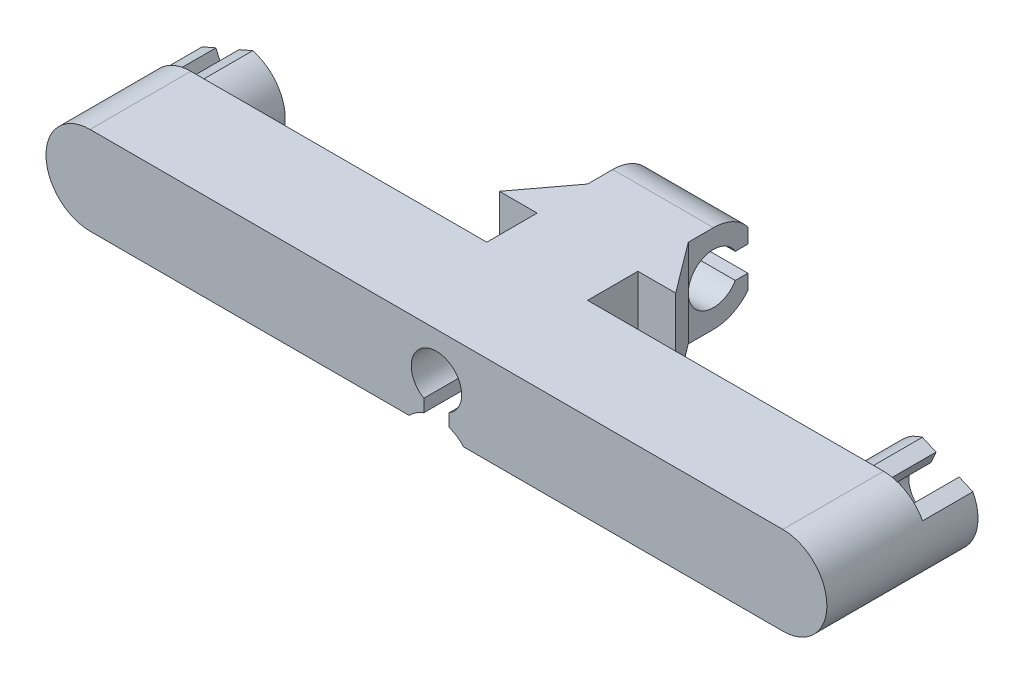
SolidWorks part; units mm, degrees
ref_plane "前视基准面" through (0, 0, 0) normal (0, 0, 1) x (1, 0, 0)
ref_plane "上视基准面" through (0, 0, 0) normal (0, 1, 0) x (1, 0, 0)
ref_plane "右视基准面" through (0, 0, 0) normal (1, 0, 0) x (0, 0, -1)
other "Configuration Table"
sketch "草图1" plane through (0, 0, 0) normal (0, 0, 1) x (1, 0, 0)
  line L0 (-404.5156, 0) -> (19821.2627, 0) construction
  line L1 (0, -404.5156) -> (0, 19821.2627) construction
  line L2 (-13.7534, 1.75) -> (13.7534, 1.75)
  line L3 (-13.7534, -1.75) -> (13.7534, -1.75)
  arc A0 (-13.7534, 1.75) -> (-13.7534, -1.75) centre (-13.7534, 0) ccw
  arc A1 (13.7534, 1.75) -> (13.7534, -1.75) centre (13.7534, 0) cw
  dimension "D1" = 3.5
  dimension "D2" = 27.5068
extrude "凸台-拉伸1" add sketch "草图1" along normal blind 4
sketch "草图2" plane through (0, 0, 0) normal (0, 0, -1) x (-1, 0, 0)
  line L0 (13.7534, -1.75) -> (-13.7534, -1.75) construction
  line L1 (-2, 1.75) -> (2, 1.75)
  line L2 (-2, 1.75) -> (-2, -1.75)
  line L3 (-2, -1.75) -> (2, -1.75)
  line L4 (2, 1.75) -> (2, -1.75)
  line L5 (-2, 1.75) -> (2, -1.75) construction
  line L6 (-2, -1.75) -> (2, 1.75) construction
  point P0 (0, 0)
  dimension "D1" = 4
extrude "凸台-拉伸2" add sketch "草图2" along normal blind 2
sketch "草图3" plane through (0, 1.75, 0) normal (0, 1, 0) x (1, 0, 0)
  line L0 (0, -1000) -> (0, 49000) construction
  line L1 (3.5, 2) -> (-3.5, 2)
  line L2 (-2, 2) -> (2, 2) construction
  line L3 (-3.5, 2) -> (-2, 4)
  line L4 (-2, 4) -> (2, 4)
  line L5 (3.5, 2) -> (2, 4)
  point P1 (0, 4)
  point P11 (0, 2)
  dimension "D1" = 3.5
  dimension "D2" = 2
  dimension "D3" = 2
extrude "凸台-拉伸3" add sketch "草图3" against normal blind 3.5
sketch "草图4" plane through (0, 0, 0) normal (0, 0, -1) x (-1, 0, 0)
  line L0 (0, -1000) -> (0, 49000) construction
  circle A0 centre (-13.7534, 0) radius 1.75
  circle A1 centre (13.7534, 0) radius 1.75
  dimension "D1" = 3.5
extrude "凸台-拉伸4" add sketch "草图4" along normal blind 2
sketch "草图5" plane through (0, 0, 4) normal (0, 0, 1) x (1, 0, 0)
  line L0 (0, -1000) -> (0, 49000) construction
  line L1 (-0.5, -1.75) -> (-0.5, -0.866)
  line L2 (-13.7534, -1.75) -> (13.7534, -1.75) construction
  line L3 (0.5, -1.75) -> (0.5, -0.866)
  line L4 (-0.5, -1.75) -> (0.5, -1.75)
  line L5 (-0.5, -1.366) -> (0.5, -1.366)
  line L6 (-0.5, -1.75) -> (-1.0795, -1.75)
  line L7 (0.5, -1.75) -> (1.0795, -1.75)
  arc A0 (0.5, -0.866) -> (-0.5, -0.866) centre (0, 0) ccw
  circle A1 centre (0, -2.75) radius 1.4715
  dimension "D1" = 2
  dimension "D2" = 0.5
  dimension "D3" = 0.5
  dimension "D4" = 1
extrude "切除-拉伸2" cut sketch "草图5" against normal blind 2 contours L1 A1 L7 | L5 L0 A1 | L0 L5 A1 | L7 L0 L5 L1 | L0 L4 L3 L5 | L7 A1 L3 | L0 A1 L3 A0 | A1 L0 A0 L1 region at (-0.25, -1.558, 4) region at (0.25, -1.558, 4) region at (-0.7089, -1.6105, 4) region at (-0.1883, -1.3309, 4) region at (0.1883, -1.3309, 4) region at (0.7089, -1.6105, 4) region at (-0.4095, -0.1135, 4) region at (0.4095, -0.1135, 4)
ref_plane "基准面1" through (0, 0, 0) normal (0, 1, 0) x (1, 0, 0)
sketch "草图6" plane through (0, 0, -2) normal (0, 0, -1) x (-1, 0, 0)
  line L0 (-1000, 0) -> (49000, 0) construction
  line L1 (0, -1000) -> (0, 49000) construction
  line L2 (13.7534, 0) -> (16.6021, 6.5623) construction
  line L3 (13.6396, 0.9935) -> (13.8387, 1.4522)
  line L4 (14.5569, 0.5953) -> (14.756, 1.054)
  line L5 (-14.5569, 0.5953) -> (-14.756, 1.054)
  line L6 (-13.6396, 0.9935) -> (-13.8387, 1.4522)
  line L7 (-14.756, 1.054) -> (-15.3007, 0.8175)
  line L8 (13.8387, 1.4522) -> (13.294, 1.6886)
  line L9 (14.756, 1.054) -> (15.3007, 0.8175)
  line L10 (-13.8387, 1.4522) -> (-13.294, 1.6886)
  circle A0 centre (13.7534, 0) radius 1.75 construction
  arc A2 (13.6396, 0.9935) -> (14.5569, 0.5953) centre (13.7534, 0) ccw
  arc A3 (14.8799, 1.3393) -> (13.9626, 1.7375) centre (13.7534, 0) ccw
  arc A4 (-13.6396, 0.9935) -> (-14.5569, 0.5953) centre (-13.7534, 0) cw
  arc A5 (-14.8799, 1.3393) -> (-13.9626, 1.7375) centre (-13.7534, 0) cw
  arc A6 (15.3007, 0.8175) -> (13.294, 1.6886) centre (13.7534, 0) ccw
  arc A7 (-15.3007, 0.8175) -> (-13.294, 1.6886) centre (-13.7534, 0) cw
  circle M8 centre (13.7534, 0) radius 1.75
  dimension "D1" = 2
  dimension "D2" = 66.535
  dimension "D3" = 0.5
  dimension "D4" = 0.5
sketch "草图7" plane through (0, 0, -4) normal (0, 0, -1) x (-1, 0, 0)
  line L4 (2, 1.75) -> (-2, 1.75)
  line L5 (-2, 1.75) -> (-2, -1.75)
  line L6 (-2, -1.75) -> (2, -1.75)
  line L7 (2, -1.75) -> (2, 1.75)
  line L8 (2, 1.75) -> (-2, 1.75)
  line L9 (-2, 1.75) -> (-2, -1.75)
  line L10 (-2, -1.75) -> (2, -1.75)
  line L11 (2, -1.75) -> (2, 1.75)
  dimension "D1" = 0
extrude "凸台-拉伸5" add sketch "草图7" along normal blind 4
sketch "草图8" plane through (2, 0, 0) normal (1, 0, 0) x (0, 0, -1)
  line L0 (-996, 0) -> (49004, 0) construction
  line L1 (4, -1.75) -> (4, 1.75) construction
  line L2 (6.366, 0.5) -> (5.866, 0.5)
  line L3 (6.366, -0.5) -> (5.866, -0.5)
  line L5 (2, 1.75) -> (4, 1.75) construction
  line L6 (4, 1.75) -> (4, -1.75)
  line L7 (4, -1.75) -> (8, -1.75)
  line L8 (8, -1.75) -> (8, 1.75)
  line L9 (8, 1.75) -> (4, 1.75)
  line L10 (4, 1.75) -> (4, -1.75)
  line L11 (4, -1.75) -> (8, -1.75)
  line L12 (8, -1.75) -> (8, 1.75)
  line L13 (8, 1.75) -> (4, 1.75)
  line L14 (6.366, 0.5) -> (6.366, 1.0938)
  line L15 (6.366, -0.5) -> (6.366, -1.0938)
  arc A0 (5.866, 0.5) -> (5.866, -0.5) centre (5, 0) ccw
  arc A1 (6.366, 1.0938) -> (5, 1.75) centre (5, 0) ccw
  arc A2 (5, -1.75) -> (6.366, -1.0938) centre (5, 0) ccw
  point P5 (4, 0)
  line M14 (8, -1.75) -> (8, 1.75)
  line M15 (8, 1.75) -> (4, 1.75)
  dimension "D1" = 2
  dimension "D3" = 1
  dimension "D2" = 0
extrude "切除-拉伸4" cut sketch "草图8" against normal blind 4 contours A0 L0 L12 A1 L14 L2 M15 | L0 A0 L3 L15 A2 L11 M14 region at (2, 0.7433, -6.3781) region at (2, -0.7433, -6.3781)
ref_plane "基准面2" through (0, 0, 0) normal (1, 0, 0) x (0, 0, -1)
sketch "草图9" plane through (0, 0, 0) normal (1, 0, 0) x (0, 0, -1)
  line L0 (-996, 0) -> (49004, 0) construction
  line L1 (52, 4.2632) -> (-49731.225, -4646.5981) construction
  arc A0 (4, 0) -> (5.866, -0.5) centre (5, 0) ccw construction
  arc A1 (5.866, 0.5) -> (4, 0) centre (5, 0) ccw construction
  arc A2 (4, 0) -> (5.866, -0.5) centre (5, 0) ccw
  arc A3 (5.866, 0.5) -> (4, 0) centre (5, 0) ccw
  circle A5 centre (52, 4.2632) radius 0.5
  circle A6 centre (52, 4.2632) radius 0.5
  point P9 (6.366, 0)
  point P10 (52, 4.2632)
  dimension "D1" = 0.5
  dimension "D2" = 0
ref_axis "基准轴1" through (0, 4.2632, -52) along (0, -0.093, 0.9957)
extrude "切除-拉伸5" cut sketch "草图6" against normal blind 2 contours A7 L7 L5 A4 L6 L10 A5 | L3 A2 L4 L9 L8 M8 region at (-13.8835, 0.2996, -2) region at (13.8835, 0.2996, -2)
